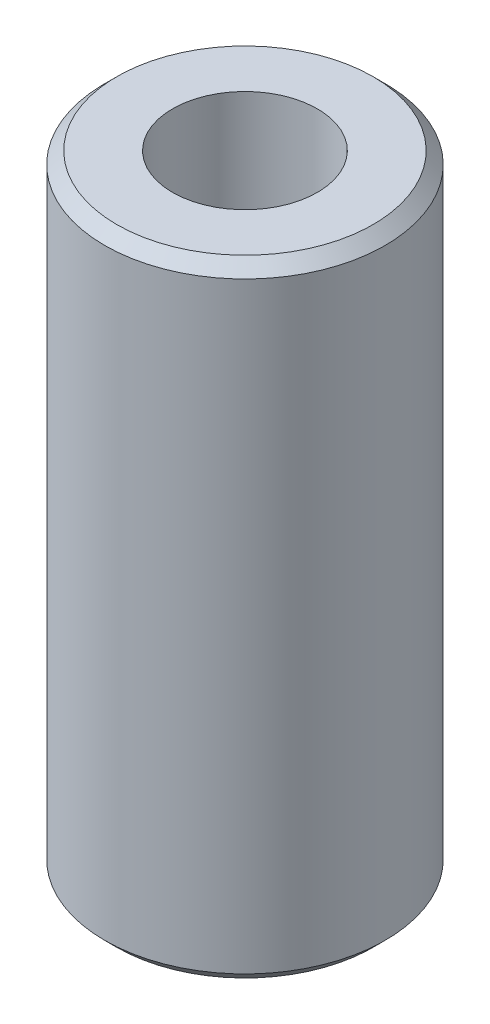
SolidWorks part; units mm, degrees
ref_plane "Front Plane" through (0, 0, 0) normal (0, 0, 1) x (1, 0, 0)
ref_plane "Top Plane" through (0, 0, 0) normal (0, 1, 0) x (1, 0, 0)
ref_plane "Right Plane" through (0, 0, 0) normal (1, 0, 0) x (0, 0, -1)
sketch "Sketch1" plane through (0, 0, 0) normal (0, 1, 0) x (1, 0, 0)
  circle A0 centre (0, 0) radius 25
  dimension "SHAFT_OD" = 50
extrude "Boss-Extrude1" add sketch "Sketch1" along normal blind 111.6099
sketch "Sketch2" plane through (0, 0, 0) normal (0, 1, 0) x (1, 0, 0)
  circle A0 centre (0, 0) radius 12.9145
  dimension "BORE_D" = 25.8291
extrude "Cut-Extrude1" cut sketch "Sketch2" along normal through all
chamfer "Chamfer1" distance 2.1496 angle 45 2 edges at (0, 111.6099, 25) (0, 0, 25)
